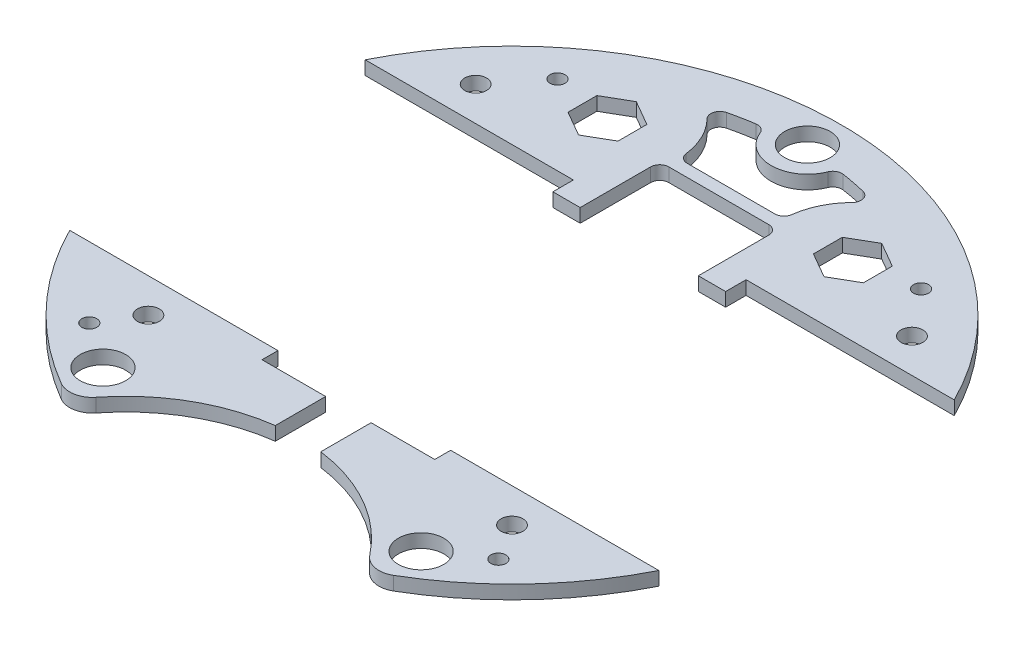
SolidWorks part; units mm, degrees
material "Acrylic (Medium-high impact)"
ref_plane "Front Plane" through (0, 0, 0) normal (0, 0, 1) x (1, 0, 0)
ref_plane "Top Plane" through (0, 0, 0) normal (0, 1, 0) x (1, 0, 0)
ref_plane "Right Plane" through (0, 0, 0) normal (1, 0, 0) x (0, 0, -1)
sketch "Sketch1" plane through (0, 0, 0) normal (0, 1, 0) x (1, 0, 0)
  line L0 (0, -85) -> (-32.4891, -64.8129) construction
  line L1 (0, -85) -> (0, 0) construction
  arc A0 (36.5434, -62.6165) -> (-36.5434, -62.6165) centre (0, 0) ccw
  arc A1 (30.0898, -61.3851) -> (-30.0898, -61.3851) centre (0, -85) ccw
  arc A2 (36.5434, -62.6165) -> (30.0898, -61.3851) centre (34.0231, -58.2982) cw
  arc A3 (-30.0898, -61.3851) -> (-36.5434, -62.6165) centre (-34.0231, -58.2982) cw
  dimension "D1" = 145
  dimension "D2" = 76.5
  dimension "D4" = 5
  dimension "D3" = 85
extrude "Boss-Extrude1" add sketch "Sketch1" along normal blind 3
sketch "solenoid placement" plane through (0, 3, 0) normal (0, 1, 0) x (1, 0, 0)
  line L4 (-19, -36) -> (19, -36)
  line L5 (-19, 28) -> (-19, -36)
  line L6 (19, 28) -> (-19, 28)
  line L7 (19, -36) -> (19, 28)
  line L8 (-19, -36) -> (19, -36)
  line L9 (-19, 28) -> (-19, -36)
  line L10 (19, 28) -> (-19, 28)
  line L11 (19, -36) -> (19, 28)
  dimension "D1" = 0
extrude "Cut-Extrude1" cut sketch "solenoid placement" against normal through all
sketch "Sketch4" plane through (0, 3, 0) normal (0, 1, 0) x (1, 0, 0)
  line L6 (19, 28) -> (-19, 28) construction
  line L10 (-13, 28) -> (13, 28)
  line L11 (13, 28) -> (13, 43.5)
  line L12 (11, 45.5) -> (-11, 45.5)
  line L13 (-13, 43.5) -> (-13, 28)
  arc A5 (13, 43.5) -> (11, 45.5) centre (11, 43.5) ccw
  arc A7 (-11, 45.5) -> (-13, 43.5) centre (-11, 43.5) ccw
  point P10 (0, 28)
  point P11 (0, 28)
  dimension "D3" = 2
  dimension "D1" = 26
  dimension "D2" = 17.5
extrude "Cut-Extrude4" cut sketch "Sketch4" against normal through all
sketch "Sketch5" plane through (0, 3, 0) normal (0, 1, 0) x (1, 0, 0)
  line L6 (0, 0) -> (0, 72.5) construction
  line L7 (-21.5, 51.1754) -> (-27, 54.3509)
  line L8 (-27, 54.3509) -> (-32.5, 51.1754)
  line L9 (-32.5, 51.1754) -> (-32.5, 44.8246)
  line L10 (-32.5, 44.8246) -> (-27, 41.6491)
  line L11 (-27, 41.6491) -> (-21.5, 44.8246)
  line L12 (-21.5, 44.8246) -> (-21.5, 51.1754)
  line L13 (21.5, 44.8246) -> (21.5, 51.1754)
  line L14 (27, 41.6491) -> (21.5, 44.8246)
  line L15 (32.5, 44.8246) -> (27, 41.6491)
  line L16 (32.5, 51.1754) -> (32.5, 44.8246)
  line L17 (27, 54.3509) -> (32.5, 51.1754)
  line L18 (21.5, 51.1754) -> (27, 54.3509)
  circle A0 centre (-27, 48) radius 5.5 construction
  arc A1 (36.5434, -62.6165) -> (-36.5434, -62.6165) centre (0, 0) ccw construction
  circle A2 centre (27, 48) radius 5.5 construction
  dimension "D1" = 11
extrude "Cut-Extrude5" cut sketch "Sketch5" against normal through all
sketch "Sketch6" plane through (0, 3, 0) normal (0, 1, 0) x (1, 0, 0)
  circle A1 centre (40, -40) radius 2.4
  circle A2 centre (40, -40) radius 2.4
  circle A3 centre (-40, -40) radius 2.4
  circle A4 centre (-40, -40) radius 2.4
  circle A5 centre (48, 40) radius 2.4
  circle A6 centre (48, 40) radius 2.4
  circle A7 centre (-48, 40) radius 2.4
  circle A8 centre (-48, 40) radius 2.4
  dimension "D1" = 0
  dimension "D2" = 0
  dimension "D3" = 0
  dimension "D4" = 0
extrude "Cut-Extrude6" cut sketch "Sketch6" against normal through all
sketch "Sketch3" plane through (0, 3, 0) normal (0, 1, 0) x (1, 0, 0)
  line L0 (-19, 28) -> (-19, 32.5)
  line L1 (72.5, -32.5) -> (-72.5, -32.5)
  line L2 (72.5, -32.5) -> (72.5, 32.5)
  line L3 (72.5, 32.5) -> (19, 32.5)
  line L4 (-72.5, -32.5) -> (-72.5, 32.5)
  line L5 (72.5, -32.5) -> (-72.5, 32.5) construction
  line L6 (72.5, 32.5) -> (-72.5, -32.5) construction
  line L7 (-19, 28) -> (19, 28)
  line L8 (19, 28) -> (19, 32.5)
  line L9 (-19, 32.5) -> (-72.5, 32.5)
  arc A0 (36.5434, -62.6165) -> (-36.5434, -62.6165) centre (0, 0) ccw construction
  point P0 (0, 0)
  dimension "D1" = 65
extrude "Cut-Extrude3" cut sketch "Sketch3" against normal through all
sketch "Sketch7" plane through (0, 3, 0) normal (0, 1, 0) x (1, 0, 0)
  line L5 (-5, 0) -> (5, 0)
  line L6 (-5, 0) -> (-5, -50)
  line L7 (-5, -50) -> (5, -50)
  line L8 (5, 0) -> (5, -50)
  point P4 (0, 0)
  dimension "D1" = 10
  dimension "D2" = 50
extrude "Cut-Extrude7" cut sketch "Sketch7" against normal through all
sketch "Sketch9" plane through (0, 3, 0) normal (0, -1, 0) x (1, 0, 0)
  circle A1 centre (35, 55) radius 5
  circle A2 centre (35, 55) radius 5
  circle A3 centre (-35, 55) radius 5
  circle A4 centre (-35, 55) radius 5
  dimension "D1" = 0
  dimension "D2" = 0
extrude "Cut-Extrude11" cut sketch "Sketch9" along normal through all
sketch "Sketch10" plane through (0, 3, 0) normal (0, 1, 0) x (1, 0, 0)
  circle A1 centre (0, 65) radius 5
  circle A2 centre (0, 65) radius 5
  dimension "D1" = 0
extrude "Cut-Extrude12" cut sketch "Sketch10" against normal through all and the other way through all
sketch "Sketch11" plane through (0, 3, 0) normal (0, 1, 0) x (1, 0, 0)
  line L0 (0, 0) -> (0, -22.1714) construction
  circle A0 centre (45, -48) radius 1.65
  circle A1 centre (-45, -48) radius 1.65
  circle A2 centre (40, 50) radius 1.65
  circle A4 centre (-40, 50) radius 1.65
  dimension "D3" = 3.3
  dimension "D1" = 45
  dimension "D2" = 48
  dimension "D4" = 40
  dimension "D5" = 50
extrude "Cut-Extrude13" cut sketch "Sketch11" against normal through all
sketch "Sketch13" plane through (0, 3, 0) normal (0, 1, 0) x (1, 0, 0)
  line L10 (-11.5013, 48.2) -> (11.5013, 48.2)
  line L11 (-9.6388, 48.2) -> (9.6388, 48.2)
  arc A8 (14.9949, 62.2186) -> (15.9519, 58.8715) centre (14.5263, 60.2743) cw
  arc A9 (7.4323, 62.04) -> (9.59, 63.2774) centre (9.2903, 61.3) cw
  arc A10 (9.6388, 48.2) -> (11.623, 49.9486) centre (9.6388, 50.2) ccw
  arc A11 (-9.6388, 48.2) -> (-11.623, 49.9486) centre (-9.6388, 50.2) cw
  arc A28 (-9.59, 63.2774) -> (-7.4323, 62.04) centre (-9.2903, 61.3) cw
  arc A29 (-11.5013, 48.2) -> (-18.8249, 61.1688) centre (-27, 48) ccw
  arc A30 (-7.861, 63.5154) -> (-18.8249, 61.1688) centre (0, 0) ccw
  arc A31 (-7.861, 63.5154) -> (7.861, 63.5154) centre (0, 65) ccw
  arc A32 (18.8249, 61.1688) -> (7.861, 63.5154) centre (0, 0) ccw
  arc A33 (18.8249, 61.1688) -> (11.5013, 48.2) centre (27, 48) ccw
  arc A34 (-11.623, 49.9486) -> (-15.9519, 58.8715) centre (-27, 48) ccw
  arc A35 (-9.59, 63.2774) -> (-14.9949, 62.2186) centre (0, 0) ccw
  arc A36 (-7.4323, 62.04) -> (7.4323, 62.04) centre (0, 65) ccw
  arc A37 (14.9949, 62.2186) -> (9.59, 63.2774) centre (0, 0) ccw
  arc A38 (15.9519, 58.8715) -> (11.623, 49.9486) centre (27, 48) ccw
  arc A39 (-15.9519, 58.8715) -> (-14.9949, 62.2186) centre (-14.5263, 60.2743) cw
  dimension "D2" = 2
  dimension "D1" = 0
extrude "Cut-Extrude14" cut sketch "Sketch13" against normal through all contours A38 A37 A36 A35 A34 L11 region at (0, 3, -55.216)
equation "\"smallPulleyTeeth\"= 30"
equation "\"largePulleyTeeth\"= 30"
equation "\"eighthThick\"= 3.0mm"
equation "\"sixteenthThick\"= 1.7mm"
equation "\"quarterThick\"=6.0mm"
equation "\"OD\"= 145mm"
equation "\"puckAngle\"= 60.5deg"
equation "\"D1@Sketch1\"=\"OD\""
equation "\"puckDiam\"= 76.5mm"
equation "\"D2@Sketch1\"=\"puckDiam\""
equation "\"D1@Boss-Extrude1\"=\"eighthThick\""
equation "\"axlePress\"= 5.9mm"
equation "\"press\"= 0.2mm"
equation "\"wheelClear\"= 0.3mm"
equation "\"10-32clear\"= 4.8mm"
equation "\"6-32clear\"= 3.3mm"
equation "\"8-32clear\"= 4.0mm"
equation "\"wheelHeight\"= 22mm"
equation "\"wheelWell\"= 65mm"
equation "\"D1@Sketch3\"=\"wheelWell\""
equation "\"puckDist\"= 85mm"
equation "\"scoopFillet\"= 5mm"
equation "\"4-40clear\"= 3.0mm"
equation "\"D3@Sketch1\"=\"puckDist\""
equation "\"D4@Sketch1\"=\"scoopFillet\""
equation "\"D3@Sketch11\"=\"6-32clear\""
